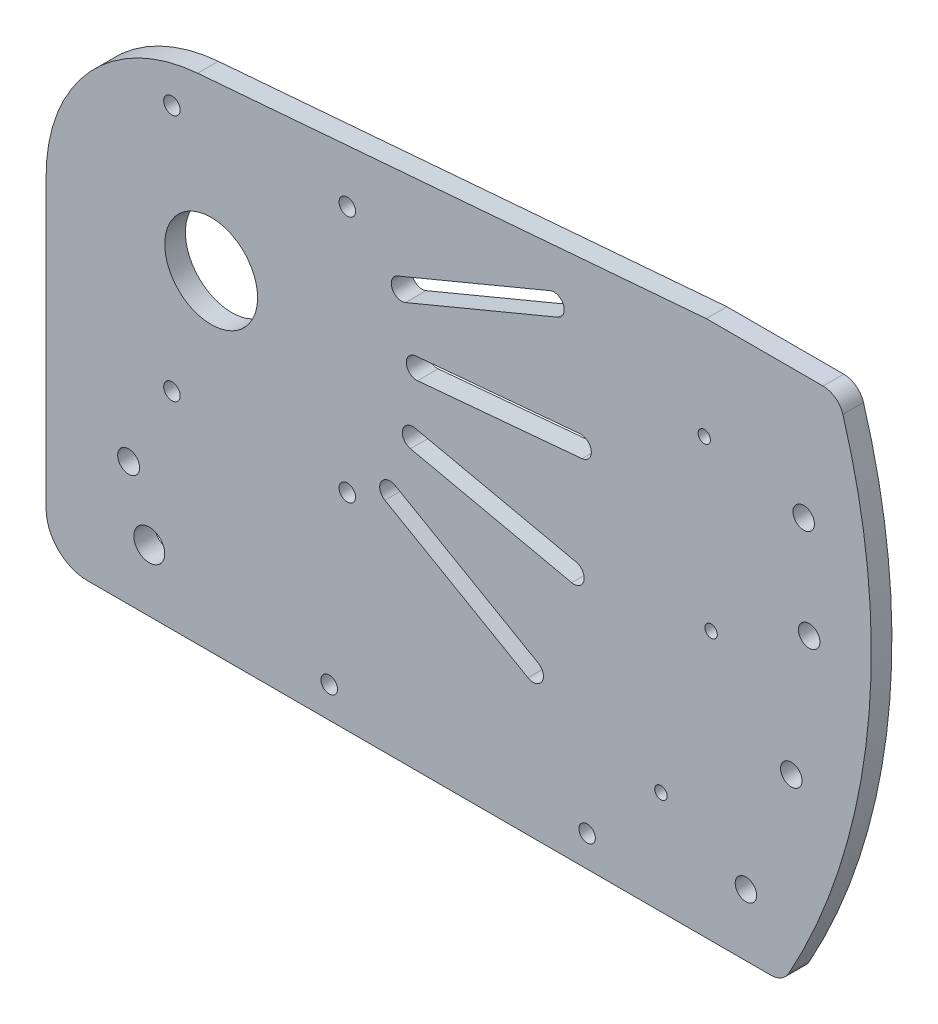
SolidWorks part; units mm, degrees
ref_plane "Front Plane" through (0, 0, 0) normal (0, 0, 1) x (1, 0, 0)
ref_plane "Top Plane" through (0, 0, 0) normal (0, 1, 0) x (1, 0, 0)
ref_plane "Right Plane" through (0, 0, 0) normal (1, 0, 0) x (0, 0, -1)
sketch "Sketch1" plane through (0, 0, 0) normal (0, 0, 1) x (1, 0, 0)
  line L0 (0, 0) -> (164.6108, -82.55) construction
  line L1 (152.4, 63.5) -> (188.3714, 63.5)
  line L2 (-50.8, 0) -> (-50.8, -88.9)
  line L3 (-38.1, -101.6) -> (172.2712, -101.6)
  line L4 (0, 0) -> (178.576, -44.9649) construction
  line L5 (0, 0) -> (152.4, 63.5)
  line L6 (58.6154, 24.4231) -> (105.5077, 43.9615) construction
  line L7 (57.3942, 27.3538) -> (104.2865, 46.8923)
  line L8 (152.4, 63.5) -> (-4.1622, 50.6292)
  line L9 (59.8365, 21.4923) -> (106.7288, 41.0308)
  line L10 (63.2466, 5.6667) -> (113.844, 10.2001) construction
  line L11 (62.9633, 8.829) -> (113.5606, 13.3624)
  line L12 (63.53, 2.5044) -> (114.1273, 7.0378)
  line L13 (62.0234, -13.6142) -> (111.6421, -24.5055) construction
  line L14 (62.7041, -10.513) -> (112.3229, -21.4044)
  line L15 (61.3427, -16.7154) -> (110.9614, -27.6067)
  line L16 (55.0589, -31.6349) -> (99.106, -56.9428) construction
  line L17 (56.6407, -28.8819) -> (100.6878, -54.1898)
  line L18 (53.4772, -34.3878) -> (97.5243, -59.6957)
  line L19 (0, 0) -> (58.6154, 24.4231) construction
  line L20 (0, 0) -> (63.2466, 5.6667) construction
  circle A0 centre (0, 0) radius 14.2875
  circle A1 centre (0, 0) radius 50.8
  arc A2 (130.1363, -101.6) -> (152.4, 63.5) centre (0, 0) ccw
  arc A3 (-50.8, -88.9) -> (-38.1, -101.6) centre (-38.1, -88.9) ccw
  arc A4 (177.8283, -98.3226) -> (194.4479, 58.9935) centre (0, 0) ccw
  arc A5 (153.586, -101.6) -> (172.8554, 63.5) centre (0, 0) ccw
  circle A6 centre (164.6108, -82.55) radius 3.302
  circle A7 centre (178.576, -44.9649) radius 3.302
  circle A8 centre (184.0752, -5.2482) radius 3.302
  circle A9 centre (182.3899, 25.4) radius 3.302
  arc A10 (57.3942, 27.3538) -> (59.8365, 21.4923) centre (58.6154, 24.4231) ccw
  arc A11 (106.7288, 41.0308) -> (104.2865, 46.8923) centre (105.5077, 43.9615) ccw
  arc A12 (62.9633, 8.829) -> (63.53, 2.5044) centre (63.2466, 5.6667) ccw
  arc A13 (114.1273, 7.0378) -> (113.5606, 13.3624) centre (113.844, 10.2001) ccw
  arc A14 (62.7041, -10.513) -> (61.3427, -16.7154) centre (62.0234, -13.6142) ccw
  arc A15 (110.9614, -27.6067) -> (112.3229, -21.4044) centre (111.6421, -24.5055) ccw
  arc A16 (56.6407, -28.8819) -> (53.4772, -34.3878) centre (55.0589, -31.6349) ccw
  arc A17 (97.5243, -59.6957) -> (100.6878, -54.1898) centre (99.106, -56.9428) ccw
  arc A18 (194.4479, 58.9935) -> (188.3714, 63.5) centre (188.3714, 57.15) ccw
  arc A19 (177.8283, -98.3226) -> (172.2712, -101.6) centre (172.2712, -95.25) cw
  circle A28 centre (-25.4, -63.5) radius 3.3782
  point P19 (82.0615, 34.1923)
  point P25 (0, 0)
  point P39 (88.5453, 7.9334)
  point P51 (86.8328, -19.0599)
  point P58 (77.0825, -44.2888)
  dimension "D1" = 28.575
  dimension "D6" = 101.6
  dimension "D7" = 330.2
  dimension "D8" = 12.7
  dimension "D9" = 406.4
  dimension "D10" = 368.3
  dimension "D11" = 19.05
  dimension "D15" = 6.35
  dimension "D19" = 3.175
  dimension "D14" = 63.5
  dimension "D5" = 6.7564
  dimension "D21" = 12.5
  dimension "D12" = 6.604
  dimension "D23" = 6.604
  dimension "D2" = 63.5
  dimension "D3" = 101.6
  dimension "D4" = 50.8
  dimension "D16" = 25.4
  dimension "D17" = 63.5
  dimension "D18" = 50.8
  dimension "D22" = 17.5
  dimension "D20" = 4
  dimension "D24" = 38.1
  dimension "D13" = 3
extrude "Boss-Extrude1" add sketch "Sketch1" along normal blind 6.35 contours L1 L2 L3 A2 A1 | A1 A0 | L3 A4 L1 A2 | A1 | L3 A4 L1 | A2 L8 A1 | A1 L8 | A1 region at (75.686, -39.8105, 0) region at (71.2368, 46.383, 0) region at (165.9987, -20.6732, 0) region at (186.4219, -20.315, 0) region at (25.6747, 42.1608, 0)
sketch "Sketch2" plane through (0, 0, 6.35) normal (0, 0, 1) x (1, 0, 0)
  line L0 (19.6773, 22.86) -> (19.6773, -22.86)
  line L1 (-24.7727, 50.8) -> (51.4273, 50.8)
  line L2 (-24.7727, 50.8) -> (-24.7727, -50.8)
  line L3 (-24.7727, -50.8) -> (51.4273, -50.8)
  line L4 (51.4273, 50.8) -> (51.4273, -50.8)
  line L5 (19.6773, 22.86) -> (0, 0)
  line L6 (0, 0) -> (19.6773, -22.86)
  circle A0 centre (19.6773, 22.86) radius 22.225
  circle A1 centre (19.6773, -22.86) radius 22.225
  circle A2 centre (-12.0727, 38.1) radius 2.54
  circle A3 centre (-12.0727, -38.1) radius 2.54
  circle A4 centre (41.9023, -38.1) radius 2.54
  circle A5 centre (41.9023, 38.1) radius 2.54
  point P4 (19.6773, 0)
  dimension "D7" = 50.8
  dimension "D8" = 44.45
  dimension "D4" = 44.45
  dimension "D12" = 5.08
  dimension "D13" = 5.08
  dimension "D16" = 5.08
  dimension "D17" = 5.08
  dimension "D1" = 0
  dimension "D2" = 45.72
  dimension "D3" = 30.1625
  dimension "D5" = 31.75
  dimension "D6" = 44.45
  dimension "D9" = 50.8
  dimension "D10" = 12.7
  dimension "D11" = 9.525
  dimension "D14" = 9.525
  dimension "D15" = 12.7
  dimension "D18" = 12.7
  dimension "D19" = 12.7
  dimension "D20" = 12.7
  dimension "D21" = 12.7
extrude "Cut-Extrude1" cut sketch "Sketch2" against normal up to surface (6.35 mm away) contours A2 | A5 | A4 | A3 up to face at (82.897, -16.5294, 0)
sketch "Sketch3" plane through (0, 0, 6.35) normal (0, 0, 1) x (1, 0, 0)
  line L4 (188.3714, 63.5) -> (152.4, 63.5)
  line L5 (152.4, 63.5) -> (-4.1622, 50.6292)
  line L6 (-50.8, 0) -> (-50.8, -88.9)
  line L7 (-38.1, -101.6) -> (172.2712, -101.6)
  line L8 (188.3714, 63.5) -> (152.4, 63.5)
  line L9 (152.4, 63.5) -> (-4.1622, 50.6292)
  line L10 (-50.8, 0) -> (-50.8, -88.9)
  line L11 (-38.1, -101.6) -> (172.2712, -101.6)
  arc A0 (117.1461, -101.6) -> (137.5755, -71.5455) centre (0, 0) ccw
  circle A1 centre (151.7818, 31.75) radius 1.905
  circle A2 centre (138.444, -69.85) radius 1.905
  circle A3 centre (153.8924, -19.05) radius 1.905
  arc A4 (139.2917, -68.144) -> (153.6468, -20.9391) centre (0, 0) ccw
  arc A5 (154.1148, -17.158) -> (152.1604, 29.883) centre (0, 0) ccw
  arc A7 (-4.1622, 50.6292) -> (-50.8, 0) centre (0, 0) ccw
  arc A8 (-50.8, -88.9) -> (-38.1, -101.6) centre (-38.1, -88.9) ccw
  arc A9 (172.2712, -101.6) -> (177.8283, -98.3226) centre (172.2712, -95.25) ccw
  arc A10 (177.8283, -98.3226) -> (194.4479, 58.9935) centre (0, 0) ccw
  arc A11 (194.4479, 58.9935) -> (188.3714, 63.5) centre (188.3714, 57.15) ccw
  arc A13 (-4.1622, 50.6292) -> (-50.8, 0) centre (0, 0) ccw
  arc A14 (-50.8, -88.9) -> (-38.1, -101.6) centre (-38.1, -88.9) ccw
  arc A15 (172.2712, -101.6) -> (177.8283, -98.3226) centre (172.2712, -95.25) ccw
  arc A16 (177.8283, -98.3226) -> (194.4479, 58.9935) centre (0, 0) ccw
  arc A17 (194.4479, 58.9935) -> (188.3714, 63.5) centre (188.3714, 57.15) ccw
  arc A18 (151.3803, 33.6122) -> (141.8551, 62.6331) centre (0, 0) ccw
  point P3 (138.444, -69.85)
  point P6 (151.7818, 31.75)
  point P9 (153.8924, -19.05)
  dimension "D2" = 310.134
  dimension "D5" = 3.81
  dimension "D6" = 3.81
  dimension "D7" = 3.81
  dimension "D3" = 31.75
  dimension "D4" = 31.75
  dimension "D8" = 50.8
  dimension "D9" = 50.8
  dimension "D1" = 0
extrude "Cut-Extrude2" cut sketch "Sketch3" against normal through all contours A1 | A3 | A2 region at (151.7818, 31.75, 6.35) region at (153.8924, -19.05, 6.35) region at (138.444, -69.85, 6.35)
sketch "Sketch4" plane through (0, 0, 6.35) normal (0, 0, 1) x (1, 0, 0)
  line L4 (188.3714, 63.5) -> (152.4, 63.5)
  line L5 (152.4, 63.5) -> (-4.1622, 50.6292)
  line L6 (-50.8, 0) -> (-50.8, -88.9)
  line L7 (-38.1, -101.6) -> (172.2712, -101.6)
  line L8 (188.3714, 63.5) -> (152.4, 63.5)
  line L9 (152.4, 63.5) -> (-4.1622, 50.6292)
  line L10 (-50.8, 0) -> (-50.8, -88.9)
  line L11 (-38.1, -101.6) -> (172.2712, -101.6)
  circle A0 centre (-19.05, -82.55) radius 4.7625
  arc A5 (194.4479, 58.9935) -> (188.3714, 63.5) centre (188.3714, 57.15) ccw
  arc A6 (-4.1622, 50.6292) -> (-50.8, 0) centre (0, 0) ccw
  arc A7 (-50.8, -88.9) -> (-38.1, -101.6) centre (-38.1, -88.9) ccw
  arc A8 (172.2712, -101.6) -> (177.8283, -98.3226) centre (172.2712, -95.25) ccw
  arc A9 (177.8283, -98.3226) -> (194.4479, 58.9935) centre (0, 0) ccw
  arc A10 (194.4479, 58.9935) -> (188.3714, 63.5) centre (188.3714, 57.15) ccw
  arc A11 (-4.1622, 50.6292) -> (-50.8, 0) centre (0, 0) ccw
  arc A12 (-50.8, -88.9) -> (-38.1, -101.6) centre (-38.1, -88.9) ccw
  arc A13 (172.2712, -101.6) -> (177.8283, -98.3226) centre (172.2712, -95.25) ccw
  arc A14 (177.8283, -98.3226) -> (194.4479, 58.9935) centre (0, 0) ccw
  dimension "D2" = 9.525
  dimension "D3" = 6.35
  dimension "D4" = 19.05
  dimension "D1" = 0
extrude "Cut-Extrude3" cut sketch "Sketch4" against normal up to surface (6.35 mm away) contours A0 region at (-19.05, -82.55, 6.35) up to face at (155.7974, -19.05, 0)
sketch "Sketch5" plane through (0, 0, 0) normal (0, 0, -1) x (-1, 0, 0)
  line L0 (50.8, 0) -> (50.8, -88.9) construction
  line L1 (38.1, -101.6) -> (-172.2712, -101.6) construction
  circle A0 centre (-36.3474, -92.075) radius 2.54
  circle A1 centre (-115.7224, -92.075) radius 2.54
  dimension "D2" = 5.08
  dimension "D4" = 5.08
  dimension "D1" = 87.1474
  dimension "D3" = 79.375
  dimension "D5" = 0
  dimension "D6" = 9.525
extrude "Cut-Extrude4" cut sketch "Sketch5" against normal up to surface (6.35 mm away) up to face at (-14.2875, -82.55, 6.35)
